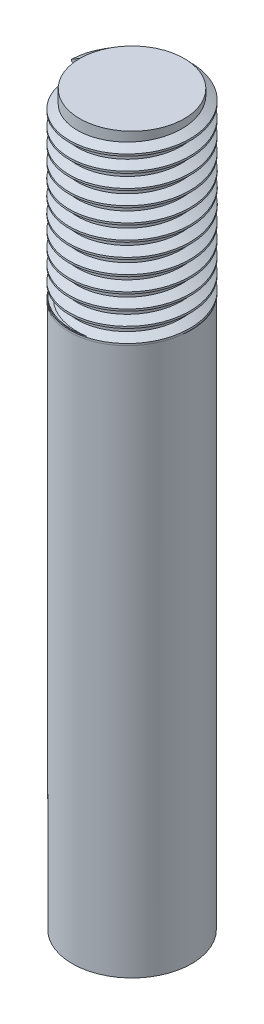
SolidWorks part; units mm, degrees
ref_plane "Front Plane" through (0, 0, 0) normal (0, 0, 1) x (1, 0, 0)
ref_plane "Top Plane" through (0, 0, 0) normal (0, 1, 0) x (1, 0, 0)
ref_plane "Right Plane" through (0, 0, 0) normal (1, 0, 0) x (0, 0, -1)
sketch "Sketch1" plane through (0, 0, 0) normal (0, 1, 0) x (1, 0, 0)
  circle A0 centre (0, 0) radius 10
  dimension "D1" = 20
extrude "Boss-Extrude1" add sketch "Sketch1" along normal blind 122
sketch "Sketch4" plane through (0, 122, 0) normal (0, 1, 0) x (1, 0, 0)
  circle A0 centre (0, 0) radius 8.75
  circle A1 centre (0, 0) radius 10
extrude "Cut-Extrude1" cut sketch "Sketch4" against normal blind 30
thread "Thread2" pitch 2.5 method extrude profile "Thread Profile2" start angle 0, offset 0, length 30, pitch 2.5, diameter 17.5
ref_plane "Plane2" through (-8.75, 122, 0) normal (0, 0, 1) x (-1, 0, 0)
sketch "Thread Profile2" plane through (-8.75, 122, 0) normal (0, 0, 1) x (-1, 0, 0)
  line L0 (0, 0) -> (0, 2.5) construction
  line L1 (0, 0) -> (1.3532, 0.7812)
  line L2 (1.3532, 0.7812) -> (1.3532, 1.0937)
  line L3 (1.3532, 1.0937) -> (0, 1.875)
  line L4 (1.3532, 0.9375) -> (0, 0.9375) construction
  line L11 (0, 0) -> (0, 1.875)
  point P2 (0, 0)
  dimension "Pitch" = 2.5
  dimension "Profile_Angle" = 60
  dimension "Profile_Land" = 0.3125
  dimension "Profile_Height" = 1.3532
sketch "Sketch7" plane through (0, 0, 0) normal (0, -1, 0) x (1, 0, 0)
  circle A0 centre (0, 0) radius 3.375
extrude "Cut-Extrude2" cut sketch "Sketch7" against normal blind 30
thread "Thread3" pitch 1.25 method cut profile "Thread Profile3" start angle 0, offset 0, length 30, pitch 1.25, diameter 6.75
ref_plane "Plane3" through (3.375, 0, 0) normal (0, 0, 1) x (1, 0, 0)
sketch "Thread Profile3" plane through (3.375, 0, 0) normal (0, 0, 1) x (1, 0, 0)
  line L0 (0, 0) -> (0, 1.25) construction
  line L1 (0, 0) -> (0.6766, 0.3906)
  line L2 (0.6766, 0.3906) -> (0.6766, 0.5469)
  line L3 (0.6766, 0.5469) -> (0, 0.9375)
  line L4 (0.6766, 0.4687) -> (0, 0.4687) construction
  line L11 (0, 0) -> (0, 0.9375)
  point P2 (0, 0)
  dimension "Pitch" = 1.25
  dimension "Profile_Angle" = 60
  dimension "Profile_Land" = 0.1562
  dimension "Profile_Height" = 0.6766
